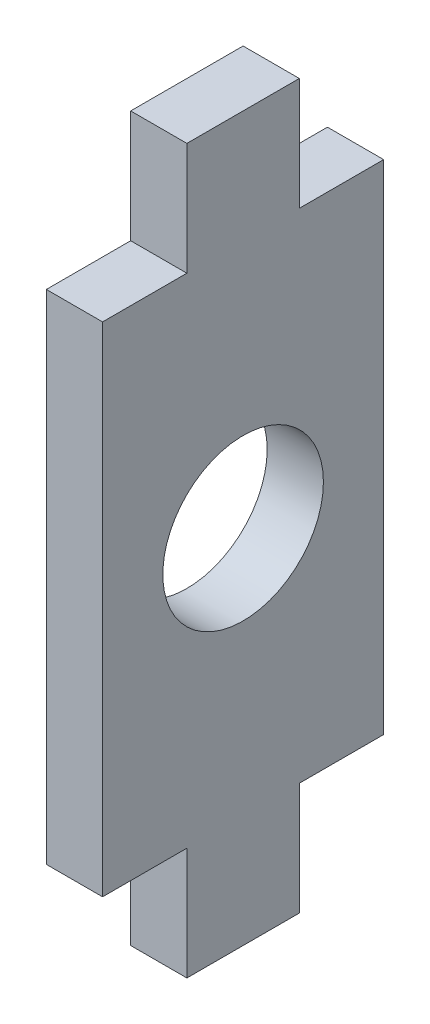
SolidWorks part; units mm, degrees
ref_plane "Front Plane" through (0, 0, 0) normal (0, 0, 1) x (1, 0, 0)
ref_plane "Top Plane" through (0, 0, 0) normal (0, 1, 0) x (1, 0, 0)
ref_plane "Right Plane" through (0, 0, 0) normal (1, 0, 0) x (0, 0, -1)
sketch "Sketch1" plane through (0, 0, 0) normal (1, 0, 0) x (0, 0, -1)
  line L1 (-17.5, -45) -> (17.5, -45)
  line L2 (-17.5, -45) -> (-17.5, 45)
  line L3 (-17.5, 45) -> (17.5, 45)
  line L4 (17.5, -45) -> (17.5, 45)
  line L5 (-17.5, -45) -> (17.5, 45) construction
  line L6 (-17.5, 45) -> (17.5, -45) construction
  line L7 (-17.5, 45) -> (-7, 45)
  line L8 (-17.5, 45) -> (-17.5, 31)
  line L9 (-17.5, 31) -> (-7, 31)
  line L10 (-7, 45) -> (-7, 31)
  line L11 (17.5, 45) -> (7, 45)
  line L12 (17.5, 45) -> (17.5, 31)
  line L13 (17.5, 31) -> (7, 31)
  line L14 (7, 45) -> (7, 31)
  line L15 (-17.5, -45) -> (-7, -45)
  line L16 (-17.5, -45) -> (-17.5, -31)
  line L17 (-17.5, -31) -> (-7, -31)
  line L18 (-7, -45) -> (-7, -31)
  line L19 (17.5, -45) -> (7, -45)
  line L20 (17.5, -45) -> (17.5, -31)
  line L21 (17.5, -31) -> (7, -31)
  line L22 (7, -45) -> (7, -31)
  point P1 (0, 0)
  dimension "D1" = 35
  dimension "D2" = 90
  dimension "D4" = 14
  dimension "D5" = 14
extrude "Boss-Extrude1" add sketch "Sketch1" along normal blind 7 contours L1 L22 L21 L4 L13 L14 L3 L10 L9 L2 L17 L18 region at (0, 0, 0)
sketch "Sketch2" plane through (7, 0, 0) normal (1, 0, 0) x (0, 0, -1)
  circle A0 centre (0, 0) radius 10
  dimension "D1" = 20
extrude "Cut-Extrude1" cut sketch "Sketch2" against normal through all
sketch "Sketch4" [suppressed] plane through (7, 0, 0) normal (1, 0, 0) x (0, 0, -1)
  circle A0 centre (0, 0) radius 14.2875
  dimension "D1" = 28.575
extrude "Cut-Extrude2" [suppressed] cut sketch "Sketch4" against normal through all
